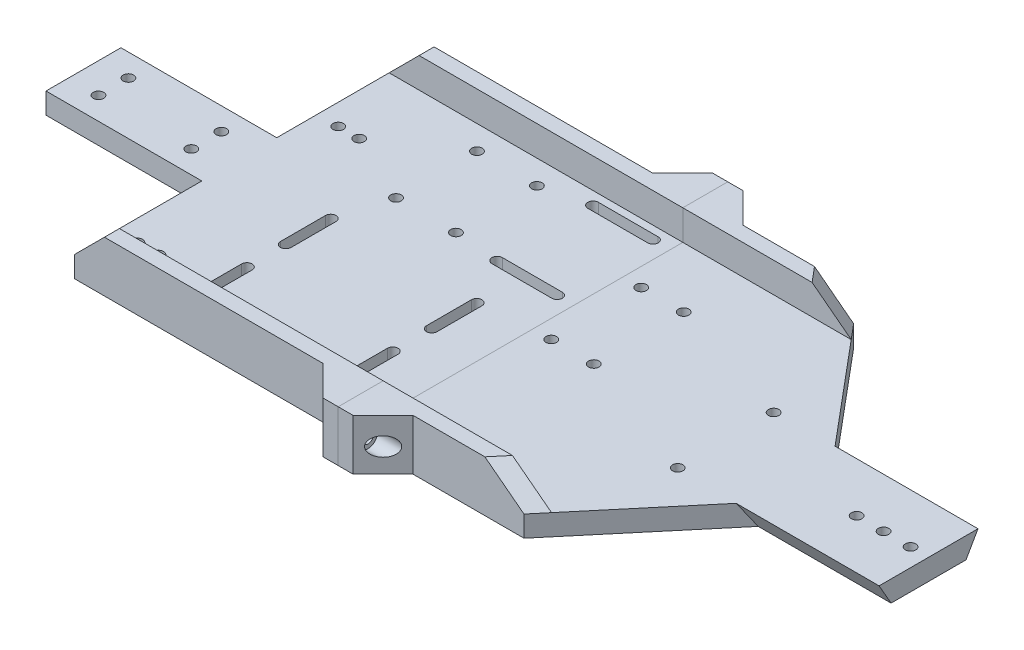
SolidWorks part; units mm, degrees
ref_plane "Alzado" through (0, 0, 0) normal (0, 0, 1) x (1, 0, 0)
ref_plane "Planta" through (0, 0, 0) normal (0, 1, 0) x (1, 0, 0)
ref_plane "Vista lateral" through (0, 0, 0) normal (1, 0, 0) x (0, 0, -1)
sketch "Croquis1" plane through (0, 0, 0) normal (0, 1, 0) x (1, 0, 0)
  line L90 (282, 25) -> (282, 0)
  line L165 (52, 0) -> (52, -42.5)
  line L166 (52, 67.5) -> (52, 25)
  line L174 (52, -42.5) -> (202, -42.5)
  line L177 (52, 67.5) -> (202, 67.5)
  line L181 (0, 12.5) -> (282, 12.5) construction
  line L186 (202, 67.5) -> (237.6617, 25)
  line L187 (202, -42.5) -> (237.6617, 0)
  line L188 (202, 67.5) -> (202, -42.5) construction
  line L189 (282, 25) -> (237.6617, 25)
  line L190 (282, 0) -> (237.6617, 0)
  line L191 (52, 25) -> (0, 25)
  line L192 (0, 25) -> (0, 0)
  line L193 (0, 0) -> (52, 0)
  dimension "D2" = 40
  dimension "D4" = 40
  dimension "D12" = 55
  dimension "D13" = 150
  dimension "D3" = 52
  dimension "D5" = 25
  dimension "D6" = 80
  dimension "D7" = 25
  dimension "D11" = 55
other "Alinear grupo1"
other "Alinear grupo2"
other "Alinear grupo3"
other "Alinear grupo4"
other "Alinear grupo5"
extrude "Saliente-Extruir1" add sketch "Croquis1" along normal mid plane 7
sketch "Croquis6" plane through (0, 3.5, 0) normal (0, 1, 0) x (1, 0, 0)
  line L1 (0, 25) -> (0, 0) construction
  line L14 (0, 12.5) -> (294.45, 12.5) construction
  line L37 (52, 67.5) -> (202, 67.5)
  line L38 (202, 67.5) -> (206.1955, 62.5)
  line L39 (237.6617, 25) -> (202, 67.5) construction
  line L40 (206.1955, 62.5) -> (52, 62.5)
  line L41 (52, 67.5) -> (52, 25) construction
  line L42 (52, 62.5) -> (52, 67.5)
  line L43 (52, -37.5) -> (52, -42.5)
  line L44 (206.1955, -37.5) -> (52, -37.5)
  line L45 (202, -42.5) -> (206.1955, -37.5)
  line L46 (52, -42.5) -> (202, -42.5)
  dimension "D1" = 5
extrude "Saliente-Extruir2" add sketch "Croquis6" along normal blind 10
sketch "Croquis9" plane through (0, -3.5, 0) normal (0, 1, 0) x (1, 0, 0)
  line L0 (150, 67.5) -> (150, -42.5) construction
  line L1 (282, 0) -> (282, 25) construction
  line L2 (52, -42.5) -> (202, -42.5) construction
  line L3 (145, -52.5) -> (135, -42.5)
  line L6 (145, -52.5) -> (155, -52.5)
  line L8 (155, -52.5) -> (165, -42.5)
  line L11 (135, -42.5) -> (165, -42.5)
  line L12 (150, -42.5) -> (150, -52.5) construction
  line L13 (0, 12.5) -> (282, 12.5) construction
  line L14 (52, 0) -> (52, -37.5) construction
  line L16 (150, 67.5) -> (150, 77.5) construction
  line L17 (135, 67.5) -> (165, 67.5)
  line L18 (155, 77.5) -> (165, 67.5)
  line L19 (145, 77.5) -> (155, 77.5)
  line L20 (145, 77.5) -> (135, 67.5)
  dimension "D1" = 10
  dimension "D2" = 30
  dimension "D3" = 10
  dimension "D4" = 98
extrude "Saliente-Extruir3" add sketch "Croquis9" along normal blind 17
sketch "Croquis15" plane through (282, 0, 0) normal (1, 0, 0) x (0, 0, -1)
  line L0 (0, -3.5) -> (0, 3.5)
  line L1 (0, 3.5) -> (-4, 3.5)
  line L2 (-37.5, 3.5) -> (0, 3.5) construction
  line L3 (-4, 3.5) -> (0, -3.5)
  line L4 (25, -3.5) -> (25, 3.5)
  line L5 (25, 3.5) -> (29, 3.5)
  line L6 (25, 3.5) -> (62.5, 3.5) construction
  line L7 (29, 3.5) -> (25, -3.5)
  dimension "D1" = 4
  dimension "D2" = 4
extrude "Saliente-Extruir4" add sketch "Croquis15" against normal up to body
sketch "Croquis7" plane through (0, 3.5, 0) normal (0, 1, 0) x (1, 0, 0)
  line L0 (294.45, 12.5) -> (0, 12.5) construction
  line L1 (234.3053, 29) -> (234.3053, -4) construction
  line L2 (234.3053, -4) -> (282, -4) construction
  line L3 (214.3053, 28.5) -> (214.3053, -3.5) construction
  line L5 (0, 25) -> (0, 0) construction
  circle A0 centre (214.3053, 28.5) radius 1.75
  circle A1 centre (214.3053, -3.5) radius 1.75
  point P10 (214.3053, 12.5)
  dimension "D1" = 3.5
  dimension "D2" = 3.5
  dimension "D3" = 32
  dimension "D4" = 20
extrude "Cortar-Extruir5" cut sketch "Croquis7" against normal through all
ref_plane "Plano1" through (0, 0, -12.5) normal (0, 0, 1) x (1, 0, 0)
chamfer "Chaflán1" distance 10 angle 45 4 edges at (52, 13.5, 40) (52, 13.5, -65) (204.0977, 13.5, -65) (204.0977, 13.5, 40)
ref_plane "Plano2" through (155, 0, 0) normal (1, 0, 0) x (0, 0, -1)
ref_plane "Plano3" through (150, 0, 0) normal (1, 0, 0) x (0, 0, -1)
sketch "Croquis12" plane through (150, 0, 0) normal (1, 0, 0) x (0, 0, -1)
  line L0 (-52.5, -3.5) -> (-42.5, -3.5) construction
  line L1 (-52.5, 13.5) -> (-52.5, -3.5) construction
  circle A0 centre (-47.5, 4.5) radius 1.75
  dimension "D1" = 3.5
  dimension "D2" = 8
  dimension "D3" = 5
extrude "Cortar-Extruir8" cut sketch "Croquis12" against normal through all both and the other way through all
sketch "Croquis14" plane through (155, 0, 0) normal (1, 0, 0) x (0, 0, -1)
  circle A0 centre (-47.5, 4.5) radius 3.1
  dimension "D1" = 6.2
extrude "Cortar-Extruir9" cut sketch "Croquis14" along normal through all
mirror "Simetría2" about plane through (150, 0, 0) normal (1, 0, 0) of "Cortar-Extruir9"
mirror "Simetría3" about plane through (0, 0, -12.5) normal (0, 0, 1) of "Cortar-Extruir8", "Simetría2", "Cortar-Extruir9"
sketch "Croquis16" plane through (0, 3.5, 0) normal (0, 1, 0) x (1, 0, 0)
  line L0 (84.36, -32.3359) -> (84.36, -17.3359) construction
  line L1 (82.61, -32.3359) -> (82.61, -17.3359)
  line L2 (86.11, -32.3359) -> (86.11, -17.3359)
  line L3 (84.36, 10.6641) -> (84.36, -4.3359) construction
  line L4 (86.11, 10.6641) -> (86.11, -4.3359)
  line L5 (82.61, 10.6641) -> (82.61, -4.3359)
  line L6 (133.06, 10.6641) -> (133.06, -4.3359) construction
  line L7 (134.81, 10.6641) -> (134.81, -4.3359)
  line L8 (131.31, 10.6641) -> (131.31, -4.3359)
  line L9 (133.06, -17.3359) -> (133.06, -32.3359) construction
  line L10 (134.81, -17.3359) -> (134.81, -32.3359)
  line L11 (131.31, -17.3359) -> (131.31, -32.3359)
  arc A0 (82.61, -32.3359) -> (86.11, -32.3359) centre (84.36, -32.3359) ccw
  arc A1 (86.11, -17.3359) -> (82.61, -17.3359) centre (84.36, -17.3359) ccw
  arc A2 (86.11, 10.6641) -> (82.61, 10.6641) centre (84.36, 10.6641) ccw
  arc A3 (82.61, -4.3359) -> (86.11, -4.3359) centre (84.36, -4.3359) ccw
  arc A4 (134.81, 10.6641) -> (131.31, 10.6641) centre (133.06, 10.6641) ccw
  arc A5 (131.31, -4.3359) -> (134.81, -4.3359) centre (133.06, -4.3359) ccw
  arc A6 (134.81, -17.3359) -> (131.31, -17.3359) centre (133.06, -17.3359) ccw
  arc A7 (131.31, -32.3359) -> (134.81, -32.3359) centre (133.06, -32.3359) ccw
  point P3 (84.36, -24.8359)
  point P8 (84.36, 3.1641)
  point P15 (84.36, 3.1641)
  point P16 (84.36, -24.8359)
  point P18 (133.06, -24.8359)
  point P21 (133.06, 3.1641)
  point P22 (133.06, 3.1641)
  point P29 (133.06, -24.8359)
  dimension "D4" = 3.5
  dimension "D1" = 15
  dimension "D2" = 15
  dimension "D3" = 3.5
  dimension "D5" = 3.5
  dimension "D6" = 3.5
extrude "Cortar-Extruir10" cut sketch "Croquis16" against normal through all
sketch "Croquis17" plane through (0, 3.5, 0) normal (0, 1, 0) x (1, 0, 0)
  line L0 (124.3, 58.25) -> (144.3, 58.25) construction
  line L1 (124.3, 60) -> (144.3, 60)
  line L2 (124.3, 56.5) -> (144.3, 56.5)
  line L3 (124.3, 26.25) -> (144.3, 26.25) construction
  line L4 (124.3, 28) -> (144.3, 28)
  line L5 (124.3, 24.5) -> (144.3, 24.5)
  line L6 (81.3, 62.5) -> (117.3, 62.5) construction
  line L7 (81.3, 62.5) -> (81.3, 19.5) construction
  line L8 (52, 62.5) -> (206.1955, 62.5) construction
  line L9 (117.3, 19.5) -> (117.3, 62.5) construction
  line L10 (81.3, 19.5) -> (117.3, 19.5) construction
  arc A0 (124.3, 60) -> (124.3, 56.5) centre (124.3, 58.25) ccw
  arc A1 (144.3, 56.5) -> (144.3, 60) centre (144.3, 58.25) ccw
  arc A2 (124.3, 28) -> (124.3, 24.5) centre (124.3, 26.25) ccw
  arc A3 (144.3, 24.5) -> (144.3, 28) centre (144.3, 26.25) ccw
  point P2 (134.3, 58.25)
  point P7 (134.3, 26.25)
  dimension "D8" = 7
  dimension "D1" = 3.5
  dimension "D2" = 3.5
  dimension "D3" = 20
  dimension "D4" = 20
  dimension "D5" = 5
  dimension "D6" = 5
  dimension "D7" = 7
extrude "Cortar-Extruir11" cut sketch "Croquis17" against normal through all
sketch "Croquis18" plane through (0, 3.5, 0) normal (0, 1, 0) x (1, 0, 0)
  circle A0 centre (10, 17.5) radius 1.75
  circle A1 centre (10, 7.5) radius 1.75
  circle A2 centre (41, 17.5) radius 1.75
  circle A3 centre (41, 7.5) radius 1.75
  circle A4 centre (59, 38.5) radius 1.75
  circle A5 centre (66, 38.5) radius 1.75
  circle A6 centre (66, -28.5) radius 1.75
  circle A7 centre (59, -28.5) radius 1.75
  circle A8 centre (89.3, 27.5) radius 1.75
  circle A9 centre (109.3, 27.5) radius 1.75
  circle A10 centre (109.3, 54.5) radius 1.75
  circle A11 centre (89.3, 54.5) radius 1.75
  circle A12 centre (156.1, 42.5) radius 1.75
  circle A13 centre (170.3, 42.5) radius 1.75
  circle A14 centre (156.1, 12.5) radius 1.75
  circle A16 centre (170.3, 12.5) radius 1.75
  circle A17 centre (214.3053, 28.5) radius 1.75
  circle A18 centre (214.3053, -3.5) radius 1.75
  circle A19 centre (258, 12.5) radius 1.75
  circle A20 centre (267, 12.5) radius 1.75
  circle A21 centre (276, 12.5) radius 1.75
extrude "Cortar-Extruir12" cut sketch "Croquis18" against normal through all
split "Partir1" trim tools "Plano3" bodies to split 137 resulting bodies 138 139
